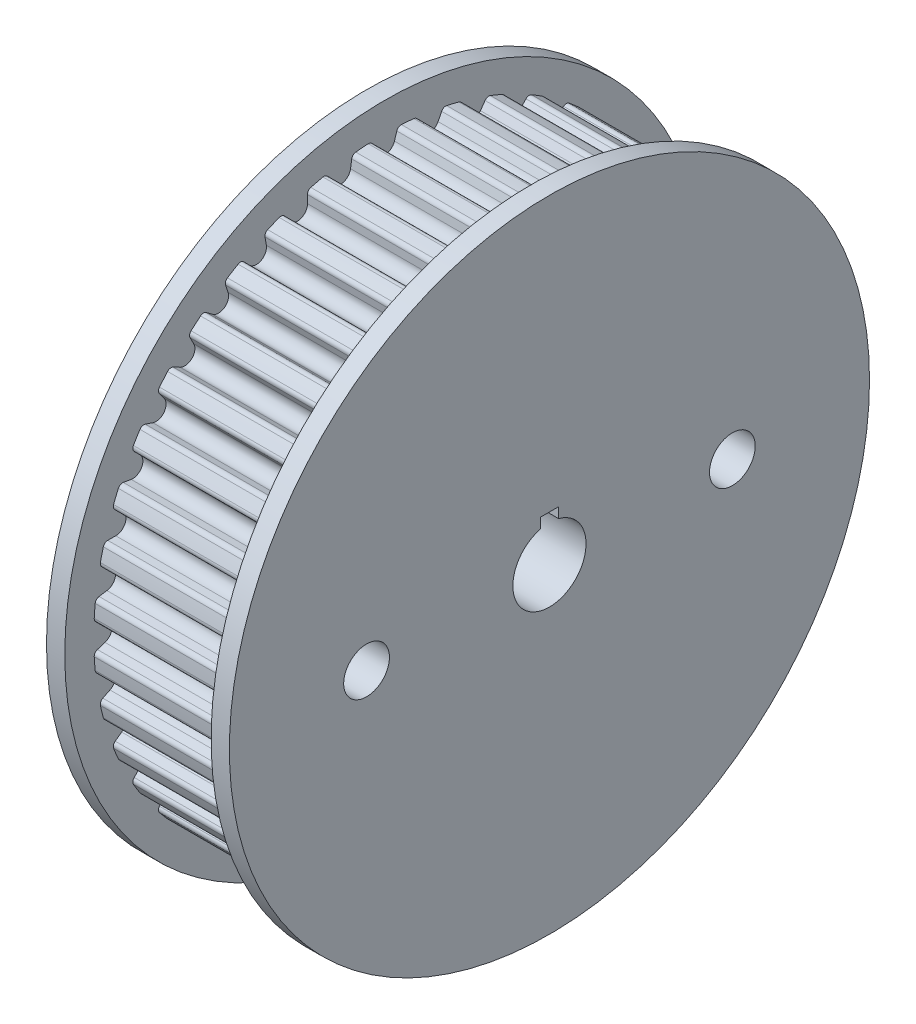
SolidWorks part; units mm, degrees
ref_plane "前视基准面" through (0, 0, 0) normal (0, 0, 1) x (1, 0, 0)
ref_plane "上视基准面" through (0, 0, 0) normal (0, 1, 0) x (1, 0, 0)
ref_plane "右视基准面" through (0, 0, 0) normal (1, 0, 0) x (0, 0, -1)
sketch "草图1" plane through (0, 0, 0) normal (0, 0, 1) x (1, 0, 0)
  line L0 (0, 0) -> (64.8368, 0) construction
  line L1 (0, 4) -> (0, 31.83)
  line L2 (0, 31.83) -> (16, 31.83)
  line L3 (16, 31.83) -> (16, 4)
  line L6 (16, 4) -> (0, 4)
  dimension "d" = 8
  dimension "da" = 63.66
  dimension "D1" = 16
revolve "旋转1" add sketch "草图1" angle 360 about L0
sketch "草图4" plane through (0, 0, 0) normal (-1, 0, 0) x (0, 0, 1)
  line L0 (0, 5) -> (0, 0) construction
  line L1 (-1, 3.873) -> (1, 3.873)
  line L2 (-1, 3.873) -> (-1, 5)
  line L3 (-1, 5) -> (1, 5)
  line L4 (1, 3.873) -> (1, 5)
  circle A1 centre (0, 0) radius 4 construction
  point P6 (0, 5)
  dimension "键槽高度" = 5
  dimension "键槽宽度" = 2
  dimension "t1" = 1
extrude "切除-拉伸1" cut sketch "草图4" against normal through all
sketch "草图6" plane through (0, 0, 0) normal (1, 0, 0) x (0, 0, -1)
  line L0 (0, 0) -> (0, 30.6512) construction
  line L1 (1.3108, 31.4293) -> (1.0491, 30.5992)
  line L2 (2.3151, 31.7457) -> (2.8004, 33.2846)
  line L3 (-2.3151, 31.7457) -> (-2.8004, 33.2846)
  line L4 (-1.3108, 31.4293) -> (-1.0491, 30.5992)
  circle A0 centre (0, 0) radius 31.83 construction
  circle A1 centre (0, 0) radius 29.83 construction
  arc A2 (-1.0491, 30.5992) -> (1.0491, 30.5992) centre (0, 30.93) ccw
  arc A3 (2.8004, 33.2846) -> (-2.8004, 33.2846) centre (0, 0) ccw
  arc A4 (1.3108, 31.4293) -> (1.8162, 31.7781) centre (1.7877, 31.279) cw
  arc A5 (1.8162, 31.7781) -> (2.3151, 31.7457) centre (0, 0) cw
  arc A6 (-1.8162, 31.7781) -> (-2.3151, 31.7457) centre (0, 0) ccw
  arc A7 (-1.3108, 31.4293) -> (-1.8162, 31.7781) centre (-1.7877, 31.279) ccw
  point P7 (0, 4.8294)
  point P8 (0, 28.6512)
  point P15 (1.4271, 31.798)
  dimension "D1" = 59.66
  dimension "ra" = 0.5
  dimension "rf" = 1.1
  dimension "hg" = 2
  dimension "D3" = 0.5
  dimension "D4" = 1.6136
  dimension "angle" = 35
  dimension "bw" = 4.8294
extrude "切除-拉伸2" cut sketch "草图6" along normal up to next
ref_axis "基准轴1" through (-1.4, 0, 0) along (1, 0, 0)
pattern_circular "阵列(圆周)3" count 40 over 360 about axis through (-1.4, 0, 0) along (1, 0, 0) of "切除-拉伸2"
sketch "草图7" plane through (0, 0, 0) normal (-1, 0, 0) x (0, 0, 1)
  line L0 (-1, 5) -> (-1, 3.873) construction
  line L1 (1, 5) -> (-1, 5) construction
  line L2 (1, 3.873) -> (1, 5) construction
  line L3 (-1, 5) -> (-1, 3.873)
  line L4 (1, 5) -> (-1, 5)
  line L5 (1, 3.873) -> (1, 5)
  circle A0 centre (0, 0) radius 35
  arc A1 (-1, 3.873) -> (1, 3.873) centre (0, 0) ccw construction
  arc A2 (-1, 3.873) -> (1, 3.873) centre (0, 0) ccw
  dimension "D1" = 70
extrude "凸台-拉伸1" add sketch "草图7" along normal blind 2
sketch "草图9" plane through (16, 0, 0) normal (1, 0, 0) x (0, 0, -1)
  line L0 (1, 5) -> (1, 3.873) construction
  line L1 (-1, 5) -> (1, 5) construction
  line L2 (-1, 3.873) -> (-1, 5) construction
  line L3 (1, 5) -> (1, 3.873)
  line L4 (-1, 5) -> (1, 5)
  line L5 (-1, 3.873) -> (-1, 5)
  arc A0 (-1, 3.873) -> (1, 3.873) centre (0, 0) ccw construction
  arc A1 (-1, 3.873) -> (1, 3.873) centre (0, 0) ccw
  circle A2 centre (0, 0) radius 35
  dimension "D1" = 70
extrude "凸台-拉伸2" add sketch "草图9" along normal blind 2
sketch "草图10" plane through (18, 0, 0) normal (1, 0, 0) x (0, 0, -1)
  line L0 (-20, 0) -> (0, 0) construction
  circle A0 centre (-20, 0) radius 2.5
  circle A1 centre (20, 0) radius 2.5
  dimension "D1" = 5
  dimension "D3" = 20
  dimension "D4" = 5
  dimension "D2" = 20
extrude "切除-拉伸3" cut sketch "草图10" against normal through all
equation "\"键槽高度@草图4\" = \"d@草图1\" / 2  + \"t1@草图4\""
equation "\"D1@草图6\" = \"da@草图1\"  - \"hg@草图6\" - \"hg@草图6\""
equation "\"D3@草图6\" = \"ra@草图6\""
